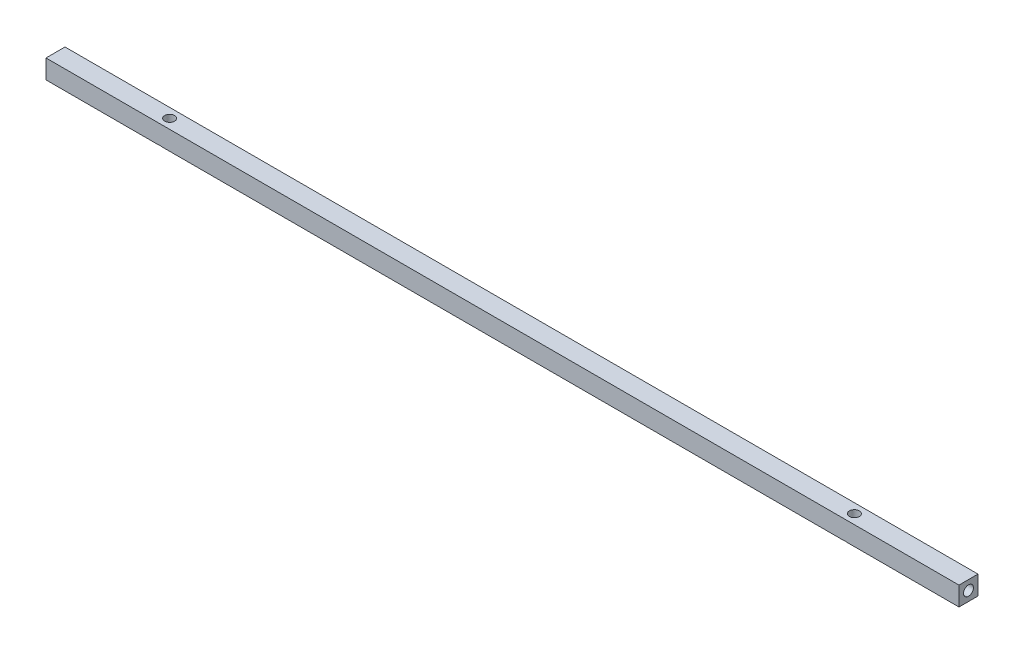
SolidWorks part; units mm, degrees
ref_plane "Front Plane" through (0, 0, 0) normal (0, 0, 1) x (1, 0, 0)
ref_plane "Top Plane" through (0, 0, 0) normal (0, 1, 0) x (1, 0, 0)
ref_plane "Right Plane" through (0, 0, 0) normal (1, 0, 0) x (0, 0, -1)
sketch "Sketch1" plane through (0, 0, 0) normal (1, 0, 0) x (0, 0, -1)
  line L1 (-3.175, -3.175) -> (3.175, -3.175)
  line L2 (-3.175, -3.175) -> (-3.175, 3.175)
  line L3 (-3.175, 3.175) -> (3.175, 3.175)
  line L4 (3.175, -3.175) -> (3.175, 3.175)
  line L5 (-3.175, -3.175) -> (3.175, 3.175) construction
  line L6 (-3.175, 3.175) -> (3.175, -3.175) construction
  point P0 (0, 0)
  dimension "D1" = 6.35
extrude "Boss-Extrude1" add sketch "Sketch1" along normal mid plane 304.8
sketch "Sketch2" plane through (152.4, 0, 0) normal (1, 0, 0) x (0, 0, -1)
  circle A0 centre (0, 0) radius 1.651
  dimension "D1" = 3.302
extrude "Cut-Extrude1" cut sketch "Sketch2" against normal blind 19.05
sketch "Sketch3" plane through (0, -3.175, 0) normal (0, -1, 0) x (-1, 0, 0)
  line L0 (-152.4, -3.175) -> (-152.4, 3.175) construction
  circle A0 centre (-114.3, 0) radius 1.651
  point P2 (0, 0)
  dimension "D1" = 3.302
  dimension "D2" = 38.1
extrude "Cut-Extrude2" cut sketch "Sketch3" against normal through all
chamfer "Chamfer1" distance 1.5875 angle 45 1 edges at (114.3, -3.175, -1.651)
mirror "Mirror1" about plane through (0, 0, 0) normal (1, 0, 0) of "Cut-Extrude2", "Cut-Extrude1", "Chamfer1"
